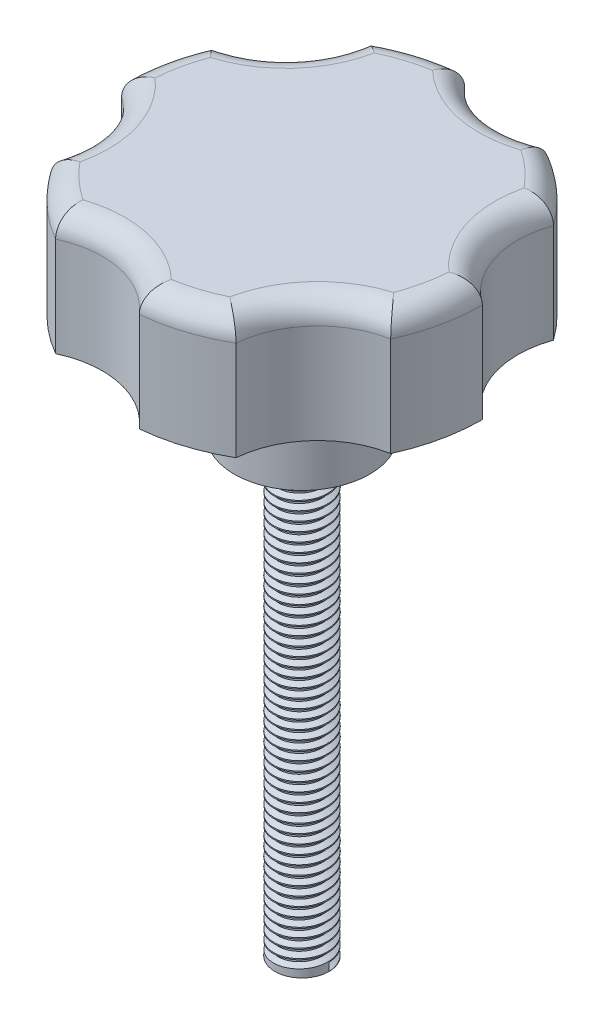
SolidWorks part; units mm, degrees
ref_plane "Front Plane" through (0, 0, 0) normal (0, 0, 1) x (1, 0, 0)
ref_plane "Top Plane" through (0, 0, 0) normal (0, 1, 0) x (1, 0, 0)
ref_plane "Right Plane" through (0, 0, 0) normal (1, 0, 0) x (0, 0, -1)
sketch "Sketch1" plane through (0, 0, 0) normal (0, 1, 0) x (1, 0, 0)
  circle A0 centre (0, 0) radius 20
  dimension "D1" = 40
extrude "Boss-Extrude1" add sketch "Sketch1" along normal blind 13.5
sketch "Sketch2" plane through (0, 13.5, 0) normal (0, 1, 0) x (1, 0, 0)
  arc A0 (16.3114, 11.5731) -> (20, 0) centre (25.725, 8.199) ccw
  circle A1 centre (0, 0) radius 20 construction
  arc A2 (20, 0) -> (16.3114, 11.5731) centre (0, 0) ccw
  dimension "D1" = 10
  dimension "D2" = 3
extrude "Cut-Extrude1" cut sketch "Sketch2" against normal up to surface (13.5 mm away) up to face at (0, 0, 20)
pattern_circular "CirPattern1" count 6 over 360 about axis through (0, 0, 0) along (0, 1, 0) of "Cut-Extrude1"
fillet "Fillet1" radius 2.5 12 edges at (-3.6279, 13.5, 16.6084) (12.5693, 13.5, 11.446) (16.1972, 13.5, -5.1624) (19.5393, 13.5, 4.2681) (6.0734, 13.5, 19.0556) (13.4659, 13.5, -14.7875) (-13.4659, 13.5, 14.7875) (-16.1972, 13.5, 5.1624) (-19.5393, 13.5, -4.2681) (-12.5693, 13.5, -11.446) (-6.0734, 13.5, -19.0556) (3.6279, 13.5, -16.6084)
sketch "Sketch4" plane through (0, 0, 0) normal (0, -1, 0) x (1, 0, 0)
  circle A0 centre (0, 0) radius 7.5
  dimension "D1" = 15
extrude "Boss-Extrude2" add sketch "Sketch4" along normal blind 11.5
sketch "Sketch5" plane through (0, -11.5, 0) normal (0, -1, 0) x (1, 0, 0)
  circle A0 centre (0, 0) radius 3
  dimension "D1" = 6
extrude "Boss-Extrude3" add sketch "Sketch5" along normal blind 50
thread "Thread1" pitch 1 profile "Thread Profile1" start angle 0, offset 0, length 50, pitch 1, diameter 6
ref_plane "Plane1" through (3, -61.5, 0) normal (0, 0, 1) x (1, 0, 0)
sketch "Thread Profile1" plane through (3, -61.5, 0) normal (0, 0, 1) x (1, 0, 0)
  line L0 (0, 0) -> (0, 1) construction
  line L11 (0, 0) -> (0, 0.875)
  line L12 (0, 0.875) -> (-0.5413, 0.5625)
  line L13 (-0.5413, 0.5625) -> (-0.5413, 0.3125)
  line L15 (-0.5413, 0.3125) -> (0, 0)
  line L17 (-0.5413, 0.4375) -> (0, 0.4375) construction
  point P2 (0, 0)
  dimension "Pitch" = 1
  dimension "Profile_Angle" = 60
  dimension "Profile_Land" = 0.25
  dimension "Profile_Height" = 0.5413
